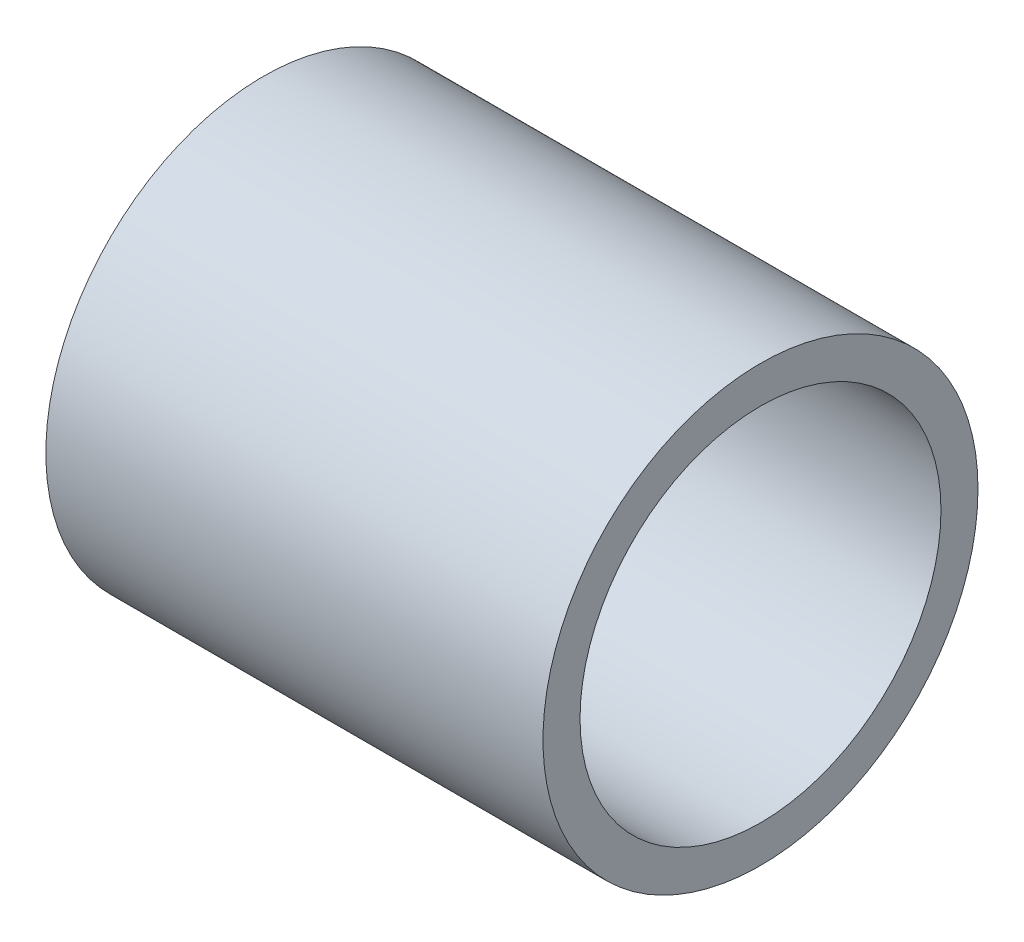
SolidWorks part; units mm, degrees
material "Tin Bearing Bronze"
ref_plane "Front Plane" through (0, 0, 0) normal (0, 0, 1) x (1, 0, 0)
ref_plane "Top Plane" through (0, 0, 0) normal (0, 1, 0) x (1, 0, 0)
ref_plane "Right Plane" through (0, 0, 0) normal (1, 0, 0) x (0, 0, -1)
sketch "Sketch1" plane through (0, 0, 0) normal (1, 0, 0) x (0, 0, -1)
  circle A0 centre (0, 0) radius 9.2202
  circle A1 centre (0, 0) radius 11.1125
  dimension "D1" = 18.4404
  dimension "D2" = 22.225
extrude "Boss-Extrude1" add sketch "Sketch1" along normal blind 25.4
